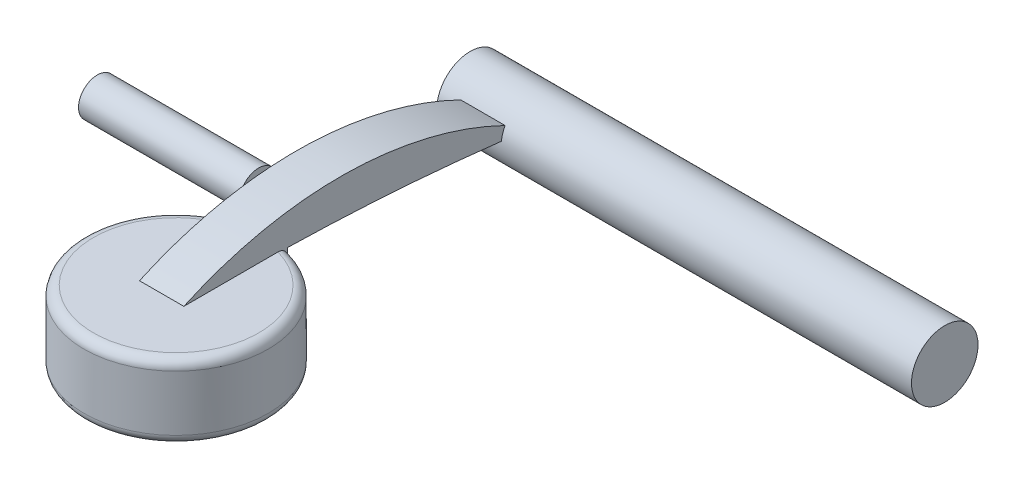
SolidWorks part; units mm, degrees
material "6061 Alloy"
ref_plane "Front Plane" through (0, 0, 0) normal (0, 0, 1) x (1, 0, 0)
ref_plane "Top Plane" through (0, 0, 0) normal (0, 1, 0) x (1, 0, 0)
ref_plane "Right Plane" through (0, 0, 0) normal (1, 0, 0) x (0, 0, -1)
sketch "Sketch1" plane through (0, 0, 0) normal (1, 0, 0) x (0, 0, -1)
  circle A0 centre (0, 0) radius 2.2479
  dimension "D1" = 4.4958
extrude "Boss-Extrude1" add sketch "Sketch1" along normal blind 32.0802
ref_plane "Plane1" through (1.3462, 0, 0) normal (1, 0, 0) x (0, 0, -1)
sketch "Sketch2" plane through (1.3462, 0, 0) normal (1, 0, 0) x (0, 0, -1)
  line L0 (-23.8506, 1.27) -> (0, 0) construction
  arc A0 (0, 0) -> (-23.8506, 1.27) centre (-20.0039, -151.0814) ccw
  arc A1 (0, 0) -> (-23.8506, 1.27) centre (-13.1173, -21.7508) ccw
  point P5 (-17.3258, 1.9972)
  point P6 (0, 0)
  point P7 (0, 0)
  point P8 (-0.147, 0)
  point P9 (-23.8506, 2.8081)
  dimension "D1" = 23.8506
  dimension "D3" = 152.4
  dimension "D4" = 25.4
  dimension "D2" = 1.27
extrude "Boss-Extrude2" add sketch "Sketch2" along normal blind 2.9972
ref_plane "Plane2" through (0, 1.3462, 0) normal (0, -1, 0) x (-1, 0, 0)
sketch "Sketch3" plane through (0, 1.3462, 0) normal (0, -1, 0) x (-1, 0, 0)
  line L0 (-2.8448, -23.8506) -> (-2.8448, -2.2479) construction
  line L1 (-4.3434, -23.8506) -> (-1.3462, -23.8506) construction
  line L2 (-32.0802, -2.2479) -> (0, -2.2479) construction
  circle A0 centre (-2.8448, -22.7076) radius 6.223
  dimension "D1" = 12.446
  dimension "D2" = 1.143
extrude "Boss-Extrude3" add sketch "Sketch3" along normal blind 5.0292
fillet "Fillet1" radius 0.635 2 edges at (9.0678, -3.683, 22.7076) (2.8448, 1.3462, 28.9306)
sketch "Sketch5" plane through (1.3462, 0, 0) normal (-1, 0, 0) x (0, 0, 1)
  circle A0 centre (15.6392, 2.6502) radius 1.27
  point P2 (14.6147, 2.5442)
  point P3 (15.1093, 2.8268)
  point P4 (15.6392, 2.6502)
  dimension "D1" = 2.54
extrude "Boss-Extrude4" add sketch "Sketch5" along normal blind 10.8966 contours A0
